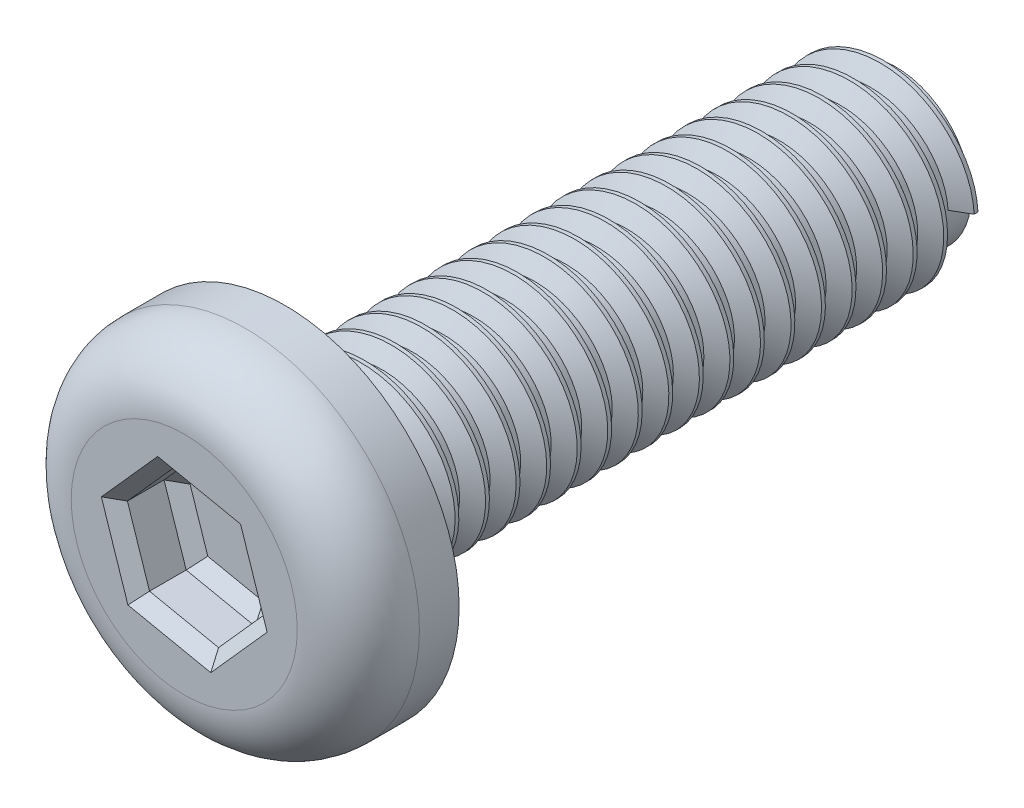
SolidWorks part; units mm, degrees
ref_plane "前视基准面" through (0, 0, 0) normal (0, 0, 1) x (1, 0, 0)
ref_plane "上视基准面" through (0, 0, 0) normal (0, 1, 0) x (1, 0, 0)
ref_plane "右视基准面" through (0, 0, 0) normal (1, 0, 0) x (0, 0, -1)
sketch "草图1" plane through (0, 0, 0) normal (0, 0, 1) x (1, 0, 0)
  circle A0 centre (0, 0) radius 2.85
  dimension "D1" = 5.7
extrude "凸台-拉伸1" add sketch "草图1" along normal blind 1.65
sketch "草图2" plane through (0, 0, 0) normal (0, 0, -1) x (-1, 0, 0)
  circle A0 centre (0, 0) radius 1.2295
  dimension "D1" = 2.459
extrude "凸台-拉伸2" add sketch "草图2" along normal blind 10
fillet "圆角1" radius 1 1 edges at (2.85, 0, 1.65)
sketch "草图3" plane through (0, 0, 1.65) normal (0, 0, 1) x (1, 0, 0)
  line L1 (0.3622, -1.0964) -> (1.1306, -0.2345)
  line L2 (1.1306, -0.2345) -> (0.7684, 0.8619)
  line L3 (0.7684, 0.8619) -> (-0.3622, 1.0964)
  line L4 (-0.3622, 1.0964) -> (-1.1306, 0.2345)
  line L5 (-1.1306, 0.2345) -> (-0.7684, -0.8619)
  line L6 (-0.7684, -0.8619) -> (0.3622, -1.0964)
  circle A0 centre (0, 0) radius 1 construction
  dimension "D1" = 2
extrude "切除-拉伸1" cut sketch "草图3" against normal blind 1
chamfer "倒角1" distance 0.2 angle 45 12 edges at (0.7464, -0.6655, 1.65) (0.9495, 0.3137, 1.65) (0.2031, 0.9792, 1.65) (-0.7464, 0.6655, 1.65) (-0.9495, -0.3137, 1.65) (-0.2031, -0.9792, 1.65) (-0.9495, -0.3137, 0.65) (-0.7464, 0.6655, 0.65) (0.2031, 0.9792, 0.65) (0.9495, 0.3137, 0.65) (0.7464, -0.6655, 0.65) (-0.2031, -0.9792, 0.65)
thread "螺纹线1" pitch 0.5 method extrude profile "螺纹线轮廓2" start angle 0, offset 0, length 0, pitch 0.5, diameter 2.459
ref_plane "基准面2" through (1.2295, 0, -10) normal (0, -1, 0) x (1, 0, 0)
sketch "螺纹线轮廓2" plane through (1.2295, 0, -10) normal (0, -1, 0) x (1, 0, 0)
  line L0 (0, 0) -> (0, 0.5) construction
  line L1 (0, 0) -> (0.2706, 0.1562)
  line L2 (0.2706, 0.1562) -> (0.2706, 0.2187)
  line L3 (0.2706, 0.2187) -> (0, 0.375)
  line L4 (0.2706, 0.1875) -> (0, 0.1875) construction
  line L11 (0, 0) -> (0, 0.375)
  point P2 (0, 0)
  dimension "Pitch" = 0.5
  dimension "Profile_Angle" = 60
  dimension "Profile_Land" = 0.0625
  dimension "Profile_Height" = 0.2706
